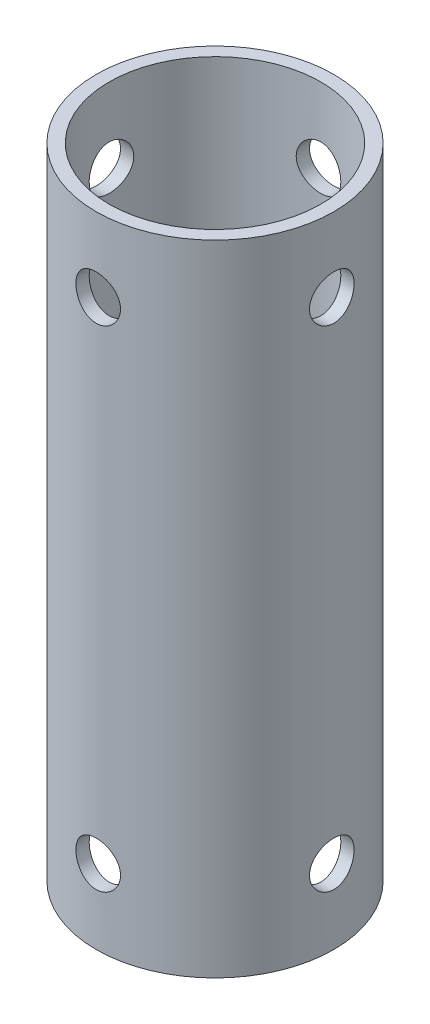
SolidWorks part; units mm, degrees
ref_plane "Front Plane" through (0, 0, 0) normal (0, 0, 1) x (1, 0, 0)
ref_plane "Top Plane" through (0, 0, 0) normal (0, 1, 0) x (1, 0, 0)
ref_plane "Right Plane" through (0, 0, 0) normal (1, 0, 0) x (0, 0, -1)
sketch "Sketch1" plane through (0, 0, 0) normal (0, 1, 0) x (1, 0, 0)
  circle A0 centre (0, 0) radius 14.25
  circle A1 centre (0, 0) radius 16
  dimension "D1" = 28.5
  dimension "D2" = 32
extrude "Boss-Extrude1" add sketch "Sketch1" along normal blind 86
ref_plane "Plane1" through (0, 0, -16) normal (0, 0, -1) x (-1, 0, 0)
sketch "Sketch2" plane through (0, 0, -16) normal (0, 0, -1) x (-1, 0, 0)
  line L0 (0, 0) -> (0, 86) construction
  line L1 (16, 86) -> (-16, 86) construction
  line L2 (-16, 0) -> (16, 0) construction
  line L4 (14.25, 86) -> (-14.25, 86) construction
  circle A0 centre (0, 10) radius 3
  circle A1 centre (0, 76) radius 3
  dimension "D2" = 6
  dimension "D3" = 6
  dimension "D1" = 10
  dimension "D4" = 10
extrude "Cut-Extrude1" cut sketch "Sketch2" against normal blind 10
ref_axis "Axis1" through (0, 86, 0) along (0, -1, 0)
pattern_circular "CirPattern1" count 4 over 360 about axis through (0, 86, 0) along (0, -1, 0) of "Cut-Extrude1"
